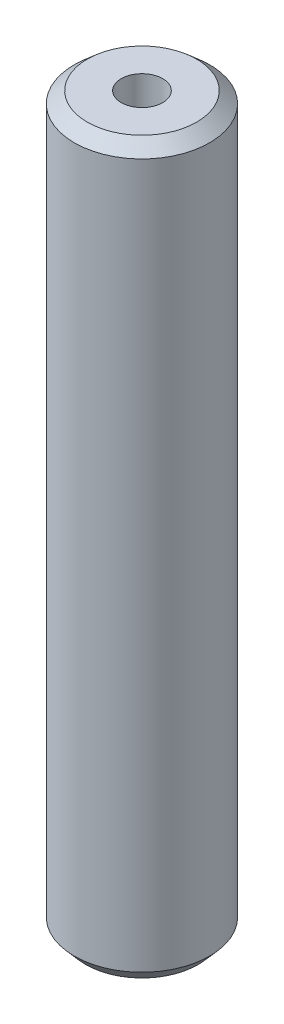
SolidWorks part; units mm, degrees
ref_plane "Front Plane" through (0, 0, 0) normal (0, 0, 1) x (1, 0, 0)
ref_plane "Top Plane" through (0, 0, 0) normal (0, 1, 0) x (1, 0, 0)
ref_plane "Right Plane" through (0, 0, 0) normal (1, 0, 0) x (0, 0, -1)
sketch "Sketch1" plane through (0, 0, 0) normal (0, 1, 0) x (1, 0, 0)
  circle A0 centre (0, 0) radius 20
  dimension "SHAFT_OD" = 40
extrude "Boss-Extrude1" add sketch "Sketch1" along normal blind 215.3901
sketch "Sketch2" plane through (0, 0, 0) normal (0, 1, 0) x (1, 0, 0)
  circle A0 centre (0, 0) radius 6.1413
  dimension "BORE_D" = 12.2826
extrude "Cut-Extrude1" cut sketch "Sketch2" along normal through all
chamfer "Chamfer1" distance 3.3568 angle 48.862 2 edges at (0, 215.3901, 20) (0, 0, 20) first distance on face at (0, 215.3901, 20) first distance on face at (0, 0, 6.1413)
